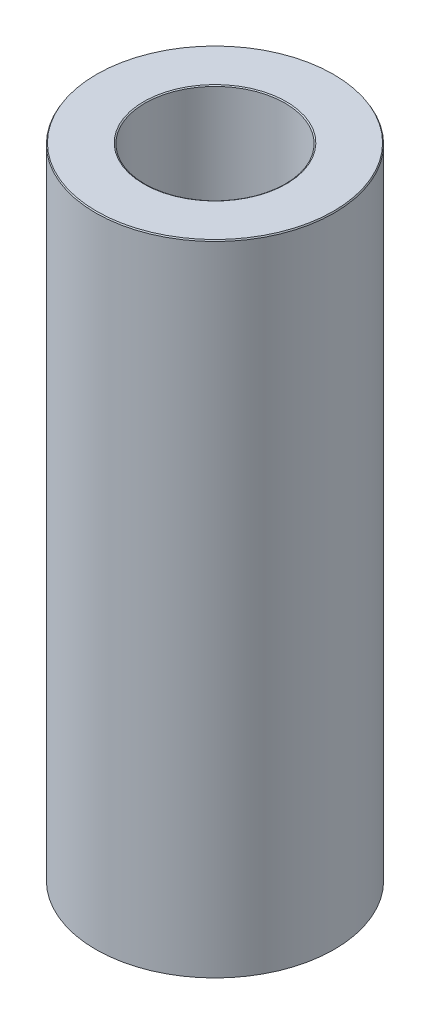
SolidWorks part; units mm, degrees
ref_plane "Front Plane" through (0, 0, 0) normal (0, 0, 1) x (1, 0, 0)
ref_plane "Top Plane" through (0, 0, 0) normal (0, 1, 0) x (1, 0, 0)
ref_plane "Right Plane" through (0, 0, 0) normal (1, 0, 0) x (0, 0, -1)
sketch "Sketch1" plane through (0, 0, 0) normal (0, 1, 0) x (1, 0, 0)
  circle A0 centre (0, 0) radius 32.5
  dimension "SLEEVE_OD" = 65
extrude "Boss-Extrude1" add sketch "Sketch1" along normal blind 174.3441
sketch "Sketch2" plane through (0, 0, 0) normal (0, 1, 0) x (1, 0, 0)
  circle A0 centre (0, 0) radius 19.1096
  dimension "BORE_D" = 38.2192
extrude "Cut-Extrude1" cut sketch "Sketch2" along normal through all
chamfer "Chamfer1" distance 0.3264 angle 31.395 4 edges at (0, 174.3441, 19.1096) (0, 0, 19.1096) (0, 0, 32.5) (0, 174.3441, 32.5) first distance on face at (0, 174.3441, 19.1096) first distance on face at (0, 0, 19.1096) first distance on face at (0, 174.3441, 32.5)
